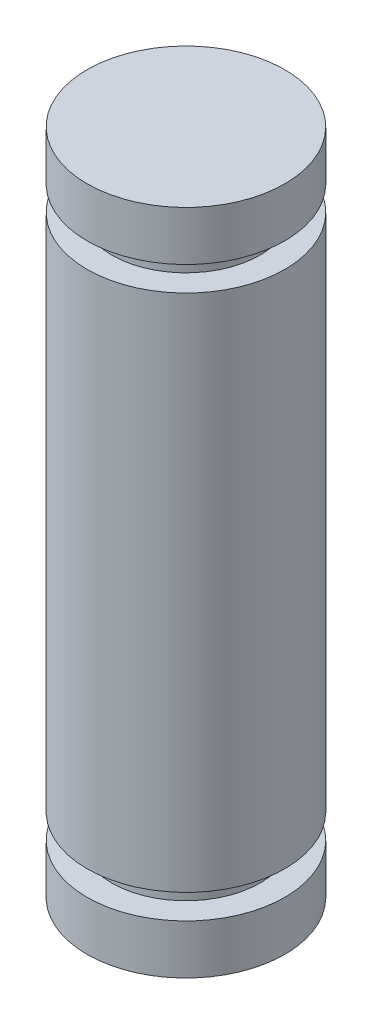
SolidWorks part; units mm, degrees
ref_plane "Front Plane" through (0, 0, 0) normal (0, 0, 1) x (1, 0, 0)
ref_plane "Top Plane" through (0, 0, 0) normal (0, 1, 0) x (1, 0, 0)
ref_plane "Right Plane" through (0, 0, 0) normal (1, 0, 0) x (0, 0, -1)
sketch "Sketch1" plane through (0, 0, 0) normal (0, 1, 0) x (1, 0, 0)
  circle A0 centre (0, 0) radius 4
  dimension "D1" = 8
extrude "Boss-Extrude1" add sketch "Sketch1" along normal blind 27
sketch "Sketch2" plane through (0, 27, 0) normal (0, 1, 0) x (1, 0, 0)
  circle A0 centre (0, 0) radius 3
  circle A1 centre (0, 0) radius 4
  dimension "D1" = 6
  dimension "D2" = 8
extrude "Cut-Extrude1" cut sketch "Sketch2" against normal blind 1 from offset 2 offset against normal yes
extrude "Cut-Extrude2" cut sketch "Sketch2<2>" against normal blind 1 from offset 24
sketch "Sketch2<2>" plane through (0, 27, 0) normal (0, 1, 0) x (1, 0, 0) same geometry as "Sketch2"
